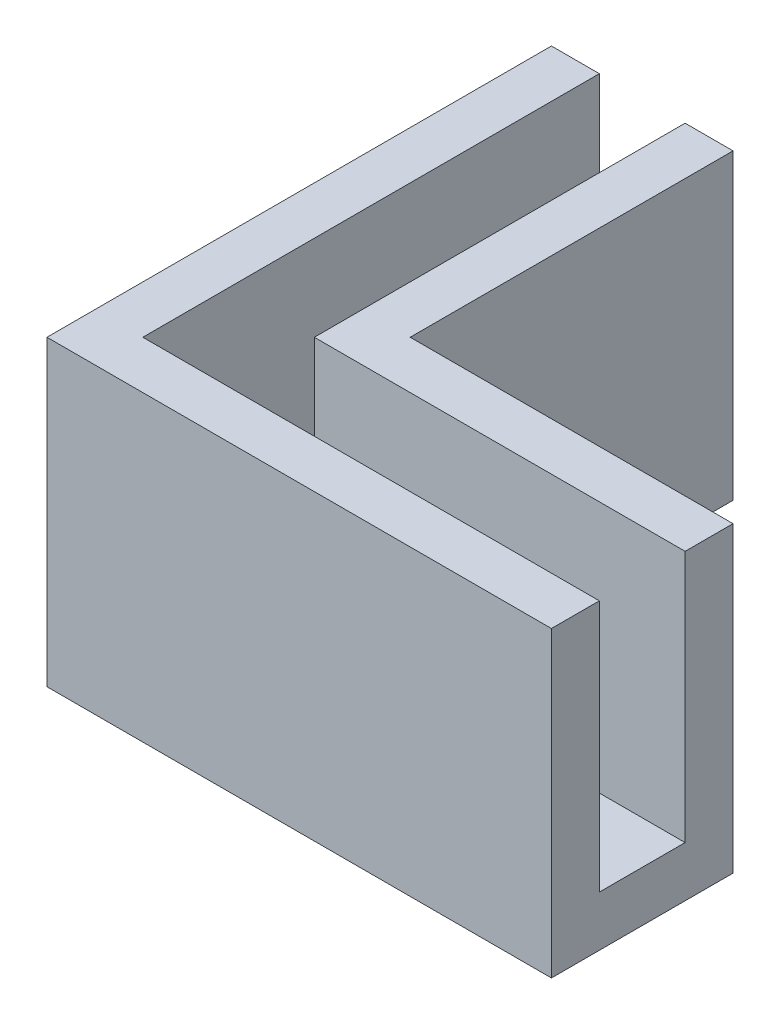
SolidWorks part; units mm, degrees
ref_plane "Front Plane" through (0, 0, 0) normal (0, 0, 1) x (1, 0, 0)
ref_plane "Top Plane" through (0, 0, 0) normal (0, 1, 0) x (1, 0, 0)
ref_plane "Right Plane" through (0, 0, 0) normal (1, 0, 0) x (0, 0, -1)
sketch "Sketch1" plane through (0, 0, 0) normal (0, 1, 0) x (1, 0, 0)
  line L0 (0, 0) -> (0, 50)
  line L1 (0, 50) -> (18, 50)
  line L2 (18, 50) -> (18, 18)
  line L3 (0, 0) -> (18, 18) construction
  line L4 (50, 18) -> (18, 18)
  line L5 (50, 0) -> (50, 18)
  line L6 (0, 0) -> (50, 0)
  line L7 (4.75, 4.75) -> (4.75, 50)
  line L8 (4.75, 50) -> (13.25, 50)
  line L9 (13.25, 50) -> (13.25, 13.25)
  line L10 (4.75, 4.75) -> (13.25, 13.25) construction
  line L11 (50, 13.25) -> (13.25, 13.25)
  line L12 (4.75, 4.75) -> (50, 4.75)
  point P9 (9, 9)
  point P12 (9, 9)
  dimension "D1" = 18
  dimension "D2" = 50
  dimension "D3" = 45
  dimension "D4" = 45
  dimension "D5" = 8.5
extrude "Boss-Extrude1" add sketch "Sketch1" along normal blind 5 contours L7 L12 L5 L11 L9 L1 region at (9, 0, -49.3601)
extrude "Boss-Extrude2" add sketch "Sketch1<3>" along normal blind 30 contours L12 L7 L1 L0 L6 L5 | L11 L5 L4 L2 L1 L9 region at (0.7071, 0, -25) region at (15.625, 0, -49.4803)
sketch "Sketch1<3>" plane through (0, 0, 0) normal (0, 1, 0) x (1, 0, 0) same geometry as "Sketch1"
